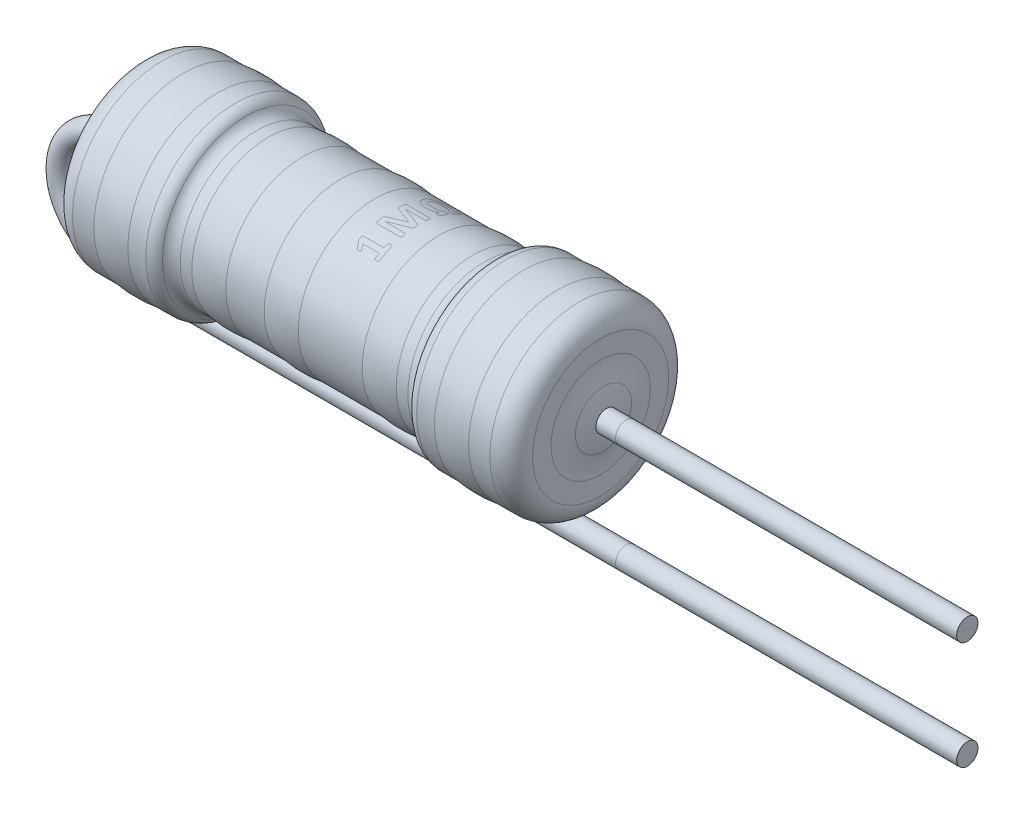
SolidWorks part; units mm, degrees
ref_plane "Front Plane" through (0, 0, 0) normal (0, 0, 1) x (1, 0, 0)
ref_plane "Top Plane" through (0, 0, 0) normal (0, 1, 0) x (1, 0, 0)
ref_plane "Right Plane" through (0, 0, 0) normal (1, 0, 0) x (0, 0, -1)
sketch "Sketch Set Wire Width" plane through (0, 0, 0) normal (0, 0, 1) x (1, 0, 0)
  line L0 (0, 0) -> (6, 0)
  line L1 (6, -2.54) -> (-6, -2.54)
  line L2 (6, 0) -> (14.0102, 0)
  line L3 (-6, 0) -> (-6, -2.54) construction
  line L4 (-6, 0) -> (-6, -2.54) construction
  line L5 (6, -2.54) -> (6, 0) construction
  line L6 (6, -2.54) -> (14.0102, -2.54)
  line L7 (14.0102, -2.54) -> (14.0102, 0) construction
  line L8 (-6, 0) -> (0, 0)
  arc A0 (-6, 0) -> (-6, -2.54) centre (-6, -1.27) ccw
  dimension "D2" = 2.54
  dimension "D3" = 30
  dimension "D1" = 12
  dimension "D4" = 6
sketch "Sketch Wire Diameter" plane through (0, 0, 0) normal (1, 0, 0) x (0, 0, -1)
  circle A0 centre (0, 0) radius 0.25
  dimension "D1" = 0.5
sweep "SET WIRE LENGTH" add profiles "Sketch Wire Diameter" path "Sketch Set Wire Width"
sketch "Sketch3" plane through (0, 0, 0) normal (0, 0, 1) x (1, 0, 0)
  line L0 (-5.4, 0) -> (5.4, 0)
  line L1 (0, 0) -> (0, 1.8) construction
  line L2 (-2.9, 1.8) -> (2.9, 1.8)
  line L3 (-5.4, 0) -> (-5.4, 1.6)
  line L4 (-4.9, 2.1) -> (-3.18, 2.1)
  line L5 (-2.9, 1.82) -> (-2.9, 1.8)
  line L6 (5.4, 0) -> (5.4, 1.6)
  line L7 (4.9, 2.1) -> (3.18, 2.1)
  line L8 (2.9, 1.82) -> (2.9, 1.8)
  arc A0 (-5.4, 1.6) -> (-4.9, 2.1) centre (-4.9, 1.6) cw
  arc A1 (5.4, 1.6) -> (4.9, 2.1) centre (4.9, 1.6) ccw
  arc A2 (-3.18, 2.1) -> (-2.9, 1.82) centre (-3.18, 1.82) cw
  arc A3 (3.18, 2.1) -> (2.9, 1.82) centre (3.18, 1.82) ccw
  dimension "D5" = 0.5
  dimension "D6" = 0.28
  dimension "D1" = 10.8
  dimension "D2" = 5.8
  dimension "D3" = 1.8
  dimension "D4" = 2.1
revolve "Revolve2" add sketch "Sketch3" angle 360 about L0
fillet "Fillet1" radius 0.3 2 edges at (2.9, 0, 1.8) (-2.9, 0, 1.8)
sketch "Sketch5" plane through (0, 0, 0) normal (0, 0, 1) x (1, 0, 0)
  line L0 (0, 0) -> (2, 0) construction
  line L1 (0, 0) -> (-0.3, 0) construction
  line L2 (-0.3, 0) -> (-2, 0) construction
  line L3 (-2, 0) -> (-4, 0) construction
  line L4 (2, 0) -> (4, 0) construction
  line L5 (-4, 0) -> (-4, 2.1) construction
  line L6 (-0.3, 0) -> (-0.3, 1.8) construction
  line L7 (-2, 0) -> (-2, 1.8) construction
  line L8 (2, 0) -> (2, 1.8) construction
  line L9 (4, 0) -> (4, 2.1) construction
  line L10 (-4, 2.1) -> (-4, 2.13) construction
  line L11 (-4.9, 2.1) -> (-3.18, 2.1) construction
  line L12 (4.9, 2.1) -> (3.18, 2.1) construction
  line L13 (-2.9, 1.8) -> (2.9, 1.8) construction
  line L14 (-2, 1.8) -> (-2, 1.83) construction
  line L17 (-4.4, 2.1) -> (-3.6, 2.1)
  line L19 (-5.4, 0) -> (5.4, 0) construction
  line L22 (-2.4, 1.8) -> (-1.6, 1.8) construction
  line L26 (-0.7, 1.8) -> (0.1, 1.8) construction
  line L30 (1.6, 1.8) -> (2.4, 1.8) construction
  line L34 (3.6, 2.1) -> (4.4, 2.1) construction
  line L36 (-0.3, 1.8) -> (-0.3, 1.83) construction
  line L37 (2, 1.8) -> (2, 1.83) construction
  line L38 (4, 2.1) -> (4, 2.13) construction
  arc A0 (-4.4, 2.1) -> (-3.6, 2.1) centre (-4, -0.5517) cw
  arc A1 (-2.4, 1.8) -> (-1.6, 1.8) centre (-2, -0.8517) cw construction
  arc A2 (-0.7, 1.8) -> (0.1, 1.8) centre (-0.3, -0.8517) cw construction
  arc A3 (1.6, 1.8) -> (2.4, 1.8) centre (2, -0.8517) cw construction
  arc A4 (3.6, 2.1) -> (4.4, 2.1) centre (4, -0.5517) cw construction
  dimension "D3" = 0.8
  dimension "D1" = 4
  dimension "D2" = 4
  dimension "D4" = 0.03
  dimension "D5" = 2
  dimension "D6" = 2
  dimension "D7" = 1.7
revolve "Band 1" add sketch "Sketch5" angle 360 about L2
sketch "Sketch8" plane through (0, 0, 0) normal (0, 0, 1) x (1, 0, 0)
  line L0 (-2.4, 1.8) -> (-1.6, 1.8) construction
  line L1 (-2.4, 1.8) -> (-1.6, 1.8)
  arc A0 (-1.6, 1.8) -> (-2.4, 1.8) centre (-2, -0.8517) ccw construction
  arc A1 (-1.6, 1.8) -> (-2.4, 1.8) centre (-2, -0.8517) ccw
revolve "Band 2" add sketch "Sketch8" angle 360 about L2
sketch "Sketch9" plane through (0, 0, 0) normal (0, 0, 1) x (1, 0, 0)
  line L0 (-0.7, 1.8) -> (0.1, 1.8) construction
  line L1 (-0.7, 1.8) -> (0.1, 1.8)
  arc A0 (0.1, 1.8) -> (-0.7, 1.8) centre (-0.3, -0.8517) ccw construction
  arc A1 (0.1, 1.8) -> (-0.7, 1.8) centre (-0.3, -0.8517) ccw
revolve "Band 3" add sketch "Sketch9" angle 360 about L2
sketch "Sketch10" plane through (0, 0, 0) normal (0, 0, 1) x (1, 0, 0)
  line L0 (1.6, 1.8) -> (2.4, 1.8) construction
  line L1 (1.6, 1.8) -> (2.4, 1.8)
  arc A0 (2.4, 1.8) -> (1.6, 1.8) centre (2, -0.8517) ccw construction
  arc A1 (2.4, 1.8) -> (1.6, 1.8) centre (2, -0.8517) ccw
revolve "Band 4" add sketch "Sketch10" angle 360 about L0
sketch "Sketch11" plane through (0, 0, 0) normal (0, 0, 1) x (1, 0, 0)
  line L0 (3.6, 2.1) -> (4.4, 2.1) construction
  line L1 (3.6, 2.1) -> (4.4, 2.1)
  arc A0 (4.4, 2.1) -> (3.6, 2.1) centre (4, -0.5517) ccw construction
  arc A1 (4.4, 2.1) -> (3.6, 2.1) centre (4, -0.5517) ccw
revolve "Band 5" add sketch "Sketch11" angle 360 about L4
sketch "Sketch12" plane through (0, 0, 0) normal (0, 0, 1) x (1, 0, 0)
  line L0 (-5.35, 0) -> (5.35, 0) construction
  line L1 (-5.35, 1) -> (-5.35, 0)
  line L2 (5.35, 1) -> (5.35, 0)
  line L3 (-5.35, 0) -> (-5.55, 0)
  line L4 (5.35, 0) -> (5.55, 0)
  arc A0 (-5.35, 1) -> (-5.55, 0) centre (-2.95, 0) ccw
  arc A1 (5.35, 1) -> (5.55, 0) centre (2.95, 0) cw
  dimension "D3" = 0.2
  dimension "D4" = 2.6
  dimension "D1" = 10.7
  dimension "D2" = 1
revolve "Revolve10" add sketch "Sketch12" angle 360 about L0
fillet "Fillet2" radius 2 2 edges at (5.4, 0, 0.8703) (-5.4, 0, -0.8703)
ref_plane "Plane2" through (0, 3, 0) normal (0, 1, 0) x (1, 0, 0)
sketch "Sketch13" plane through (0, 3, 0) normal (0, 1, 0) x (1, 0, 0)
  line L0 (0, 0) -> (1.15, 0) construction
  line L1 (1.15, 1.75) -> (1.15, -1.75) construction
  text T0 "1MΩ" font "Calibri" height 0.6
  dimension "D1" = 3.5
  dimension "D2" = 1.15
wrap "Wrap1" sketch "Sketch13" wrap type scribe source sketch "Sketch13" face at (0.1, 1.8, 0)
